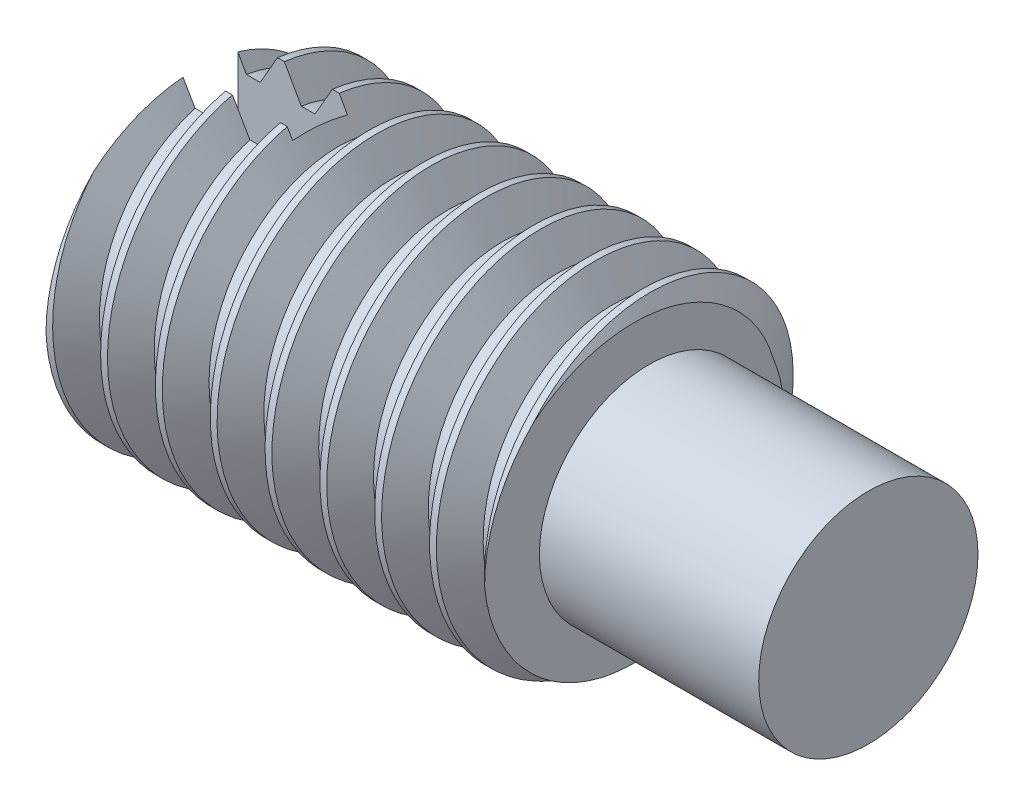
SolidWorks part; units mm, degrees
ref_plane "Front Plane" through (0, 0, 0) normal (0, 0, 1) x (1, 0, 0)
ref_plane "Top Plane" through (0, 0, 0) normal (0, 1, 0) x (1, 0, 0)
ref_plane "Right Plane" through (0, 0, 0) normal (1, 0, 0) x (0, 0, -1)
sketch "Sketch1" plane through (0, 0, 0) normal (1, 0, 0) x (0, 0, -1)
  circle A0 centre (0, 0) radius 2
  circle A1 centre (0, 0) radius 3
  dimension "D1" = 4
  dimension "D2" = 6
extrude "Boss-Extrude1" add sketch "Sketch1" along normal blind 12 contours A0 region at (0, 0, 0)
extrude "Boss-Extrude2" add sketch "Sketch1<3>" along normal blind 8
sketch "Sketch1<3>" plane through (0, 0, 0) normal (1, 0, 0) x (0, 0, -1) same geometry as "Sketch1"
sketch "Sketch2" plane through (0, 0, 0) normal (-1, 0, 0) x (0, 0, 1)
  line L1 (-0.5, 3.1875) -> (0.5, 3.1875)
  line L2 (-0.5, 3.1875) -> (-0.5, -3.1875)
  line L3 (-0.5, -3.1875) -> (0.5, -3.1875)
  line L4 (0.5, 3.1875) -> (0.5, -3.1875)
  line L5 (-0.5, 3.1875) -> (0.5, -3.1875) construction
  line L6 (-0.5, -3.1875) -> (0.5, 3.1875) construction
  point P0 (0, 0)
  dimension "D1" = 1
extrude "Cut-Extrude1" cut sketch "Sketch2" against normal blind 2
thread "Thread1" pitch 1 method cut profile "Thread Profile1" start angle 0, offset 1, length 30, pitch 1, diameter 6
ref_plane "Plane1" through (9, 0, 3) normal (0, -1, 0) x (0, 0, 1)
sketch "Thread Profile1" plane through (9, 0, 3) normal (0, -1, 0) x (0, 0, 1)
  line L0 (0, 0) -> (0, 1) construction
  line L11 (0, 0) -> (0, 0.875)
  line L12 (0, 0.875) -> (-0.5413, 0.5625)
  line L13 (-0.5413, 0.5625) -> (-0.5413, 0.3125)
  line L15 (-0.5413, 0.3125) -> (0, 0)
  line L17 (-0.5413, 0.4375) -> (0, 0.4375) construction
  point P2 (0, 0)
  dimension "Pitch" = 1
  dimension "Profile_Angle" = 60
  dimension "Profile_Land" = 0.25
  dimension "Profile_Height" = 0.5413
